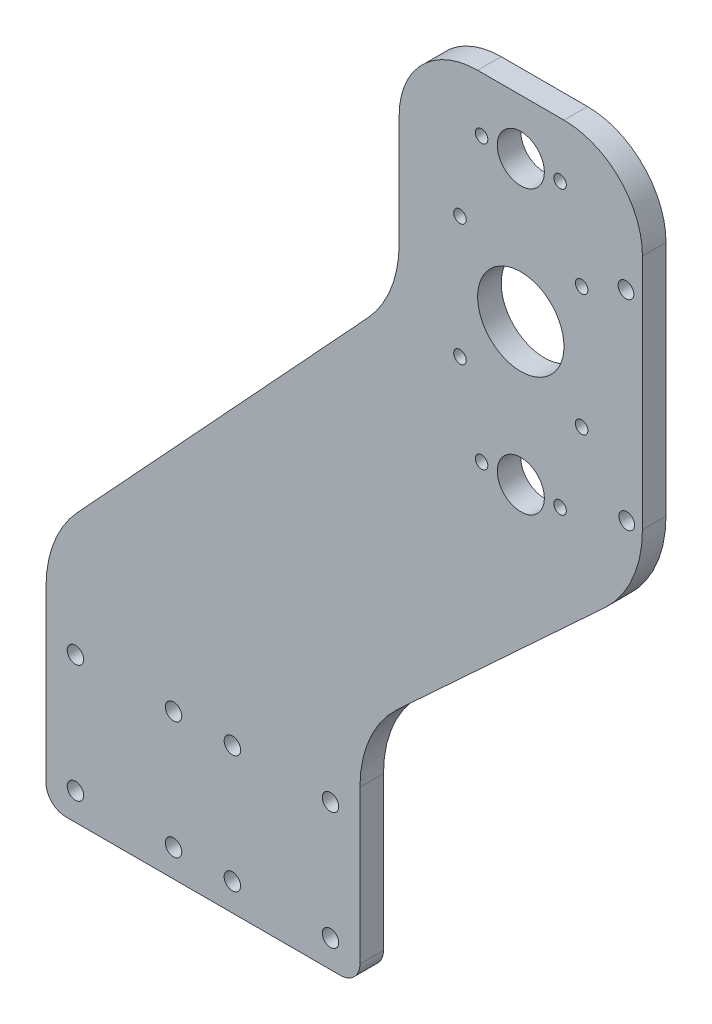
SolidWorks part; units mm, degrees
ref_plane "Front Plane" through (0, 0, 0) normal (0, 0, 1) x (1, 0, 0)
ref_plane "Top Plane" through (0, 0, 0) normal (0, 1, 0) x (1, 0, 0)
ref_plane "Right Plane" through (0, 0, 0) normal (1, 0, 0) x (0, 0, -1)
sketch "Sketch1" plane through (0, 0, 0) normal (0, 0, 1) x (1, 0, 0)
  line L0 (-23.4503, -99.2073) -> (-23.4503, -15.4242) construction
  line L1 (-58.4503, -99.2073) -> (11.5497, -99.2073)
  line L2 (-63.4503, -94.2073) -> (-63.4503, -50.959)
  line L3 (-63.4503, -94.2073) -> (-23.4503, -94.2073) construction
  line L4 (16.5497, -94.2073) -> (16.5497, -55.2061)
  line L5 (46.5497, 118.0426) -> (68.5497, 118.0426)
  line L6 (26.5497, 98.0426) -> (26.5497, 69.7942)
  line L7 (57.5497, 118.0426) -> (57.5497, 32.1026) construction
  line L8 (88.5497, 98.0426) -> (88.5497, 37.6266)
  line L9 (-43.4503, -77.2073) -> (-43.4503, -94.2073) construction
  line L10 (-55.9503, -62.2073) -> (-30.9503, -62.2073) construction
  line L11 (18.5677, 49.4176) -> (-55.4683, -30.5824)
  line L12 (78.9209, 15.6036) -> (26.1784, -33.1831)
  line L13 (-55.9503, -62.2073) -> (-55.9503, -92.2073) construction
  line L14 (-55.9503, -92.2073) -> (-30.9503, -92.2073) construction
  line L15 (-30.9503, -62.2073) -> (-30.9503, -92.2073) construction
  line L16 (-55.9503, -62.2073) -> (-30.9503, -92.2073) construction
  line L17 (-55.9503, -92.2073) -> (-30.9503, -62.2073) construction
  line L18 (57.5497, 104.0426) -> (57.5497, 32.1026) construction
  line L20 (42.0497, 52.5726) -> (73.0497, 52.5726) construction
  line L21 (42.0497, 52.5726) -> (42.0497, 83.5726) construction
  line L22 (42.0497, 83.5726) -> (73.0497, 83.5726) construction
  line L23 (73.0497, 52.5726) -> (73.0497, 83.5726) construction
  line L24 (42.0497, 52.5726) -> (73.0497, 83.5726) construction
  line L25 (42.0497, 83.5726) -> (73.0497, 52.5726) construction
  arc A0 (78.9209, 15.6036) -> (88.5497, 37.6266) centre (58.5497, 37.6266) ccw
  arc A1 (18.5677, 49.4176) -> (26.5497, 69.7942) centre (-3.4503, 69.7942) ccw
  arc A2 (16.5497, -55.2061) -> (26.1784, -33.1831) centre (46.5497, -55.2061) cw
  arc A3 (-63.4503, -50.959) -> (-55.4683, -30.5824) centre (-33.4503, -50.959) cw
  arc A4 (88.5497, 98.0426) -> (68.5497, 118.0426) centre (68.5497, 98.0426) ccw
  arc A5 (46.5497, 118.0426) -> (26.5497, 98.0426) centre (46.5497, 98.0426) ccw
  arc A6 (16.5497, -94.2073) -> (11.5497, -99.2073) centre (11.5497, -94.2073) cw
  arc A7 (-58.4503, -99.2073) -> (-63.4503, -94.2073) centre (-58.4503, -94.2073) cw
  circle A8 centre (-55.9503, -62.2073) radius 2.1
  circle A9 centre (-30.9503, -62.2073) radius 2.1
  circle A10 centre (-30.9503, -92.2073) radius 2.1
  circle A11 centre (-55.9503, -92.2073) radius 2.1
  circle A12 centre (9.0497, -92.2073) radius 2.1
  circle A13 centre (-15.9503, -92.2073) radius 2.1
  circle A14 centre (-15.9503, -62.2073) radius 2.1
  circle A15 centre (9.0497, -62.2073) radius 2.1
  circle A16 centre (57.5497, 104.0426) radius 6
  circle A17 centre (57.5497, 32.1026) radius 6
  circle A18 centre (57.5497, 68.0726) radius 11
  circle A19 centre (42.0497, 83.5726) radius 1.6
  circle A20 centre (73.0497, 83.5726) radius 1.6
  circle A21 centre (73.0497, 52.5726) radius 1.6
  circle A22 centre (42.0497, 52.5726) radius 1.6
  circle A23 centre (84.5497, 37.6266) radius 2
  circle A24 centre (84.3518, 88.5185) radius 2
  circle A25 centre (47.5497, 104.0426) radius 1.6
  circle A26 centre (47.5497, 32.1026) radius 1.6
  circle A27 centre (67.5497, 104.0426) radius 1.6
  circle A28 centre (67.5497, 32.1026) radius 1.6
  point P0 (0, 0)
  point P1 (57.5497, 82.2289)
  point P15 (26.5497, 58.0426)
  point P20 (-63.4503, -39.2073)
  point P23 (88.5497, 118.0426)
  point P26 (26.5497, 118.0426)
  point P29 (16.5497, -99.2073)
  point P32 (-63.4503, -99.2073)
  point P35 (-43.4503, -77.2073)
  dimension "D5" = 30
  dimension "D6" = 20
  dimension "D7" = 5
  dimension "D14" = 71.94
  dimension "D12" = 31
  dimension "D17" = 4
  dimension "D18" = 10
  dimension "D19" = 10
  dimension "D1" = 80
  dimension "D2" = 22
  dimension "D3" = 90
  dimension "D4" = 60
  dimension "D8" = 25
  dimension "D9" = 60
  dimension "D10" = 22
  dimension "D11" = 80
  dimension "D13" = 30
  dimension "D15" = 14
  dimension "D16" = 31
extrude "Boss-Extrude1" add sketch "Sketch1" along normal blind 6
